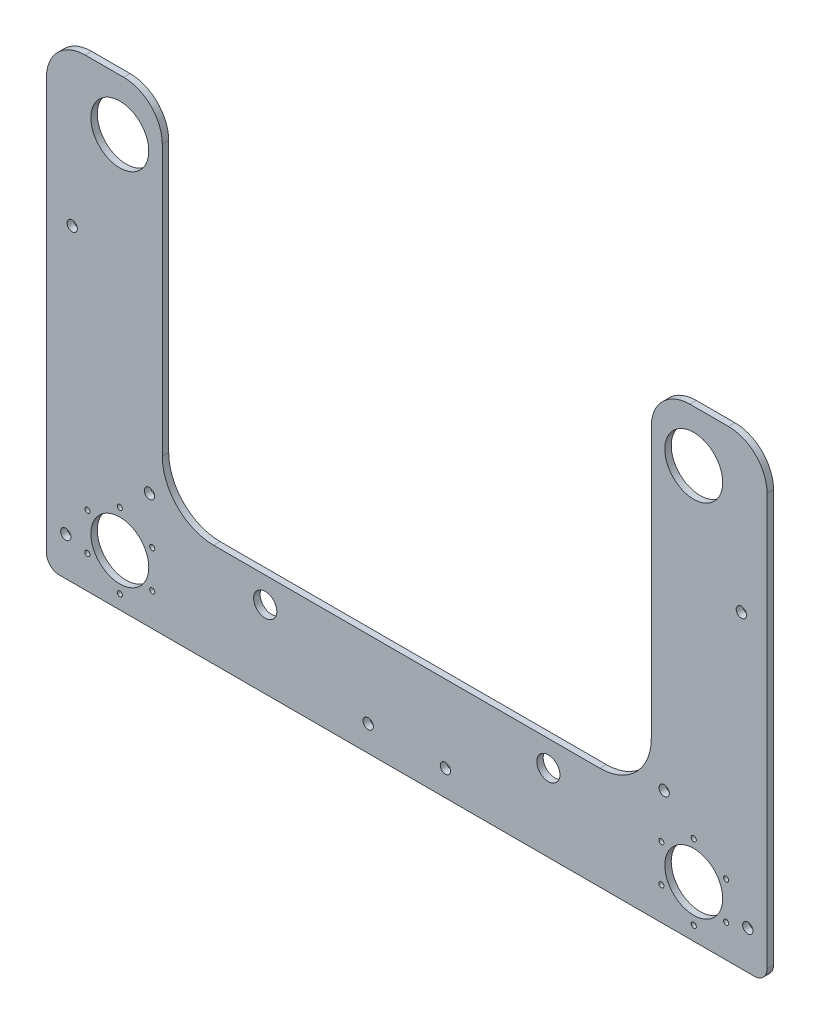
SolidWorks part; units mm, degrees
ref_plane "Front Plane" through (0, 0, 0) normal (0, 0, 1) x (1, 0, 0)
ref_plane "Top Plane" through (0, 0, 0) normal (0, 1, 0) x (1, 0, 0)
ref_plane "Right Plane" through (0, 0, 0) normal (1, 0, 0) x (0, 0, -1)
sketch "Sketch1" plane through (0, 0, 0) normal (0, 0, 1) x (1, 0, 0)
  line L5 (120.65, -152.4) -> (120.65, -6.35)
  line L6 (127, 0) -> (171.45, 0) construction
  line L7 (177.8, -6.35) -> (177.8, -222.25)
  line L10 (0, -206.2199) -> (0, -63.6275) construction
  line L11 (-54.9244, 0) -> (300.6756, 0) construction
  line L13 (12.7, -177.8) -> (95.25, -177.8)
  line L14 (12.7, -228.6) -> (171.45, -228.6)
  line L15 (141.605, -25.4) -> (141.605, -84.2822) construction
  line L16 (141.605, -25.4) -> (141.605, -127) construction
  line L17 (-141.605, -25.4) -> (-141.605, -203.2) construction
  line L18 (-141.605, -25.4) -> (-141.605, -127) construction
  line L19 (-141.605, -19.05) -> (-141.605, -77.9322) construction
  line L20 (141.605, -25.4) -> (141.605, -203.2) construction
  line L22 (-120.65, -152.4) -> (-120.65, -6.35)
  line L23 (-12.7, -177.8) -> (-95.25, -177.8)
  line L24 (-12.7, -228.6) -> (-171.45, -228.6)
  line L25 (-177.8, -6.35) -> (-177.8, -222.25)
  line L26 (-12.7, -177.8) -> (12.7, -177.8)
  line L27 (-12.7, -228.6) -> (12.7, -228.6)
  line L28 (-177.8, -6.35) -> (-177.8, 6.35)
  line L29 (-165.1, 19.05) -> (-133.35, 19.05)
  line L30 (-120.65, 6.35) -> (-120.65, -6.35)
  line L31 (120.65, 6.35) -> (120.65, -6.35)
  line L32 (177.8, -6.35) -> (177.8, 6.35)
  line L33 (165.1, 19.05) -> (133.35, 19.05)
  arc A0 (95.25, -177.8) -> (120.65, -152.4) centre (95.25, -152.4) ccw
  arc A4 (120.65, -6.35) -> (127, 0) centre (127, -6.35) cw construction
  circle A8 centre (141.605, -25.4) radius 14.2875
  circle A9 centre (141.605, -25.4) radius 38.1 construction
  arc A10 (177.8, -6.35) -> (171.45, 0) centre (171.45, -6.35) ccw construction
  arc A11 (171.45, -228.6) -> (177.8, -222.25) centre (171.45, -222.25) ccw
  arc A14 (141.605, -82.55) -> (120.9214, -78.6758) centre (141.605, -25.4) ccw construction
  arc A15 (-141.605, -82.55) -> (-120.9214, -78.6758) centre (-141.605, -25.4) cw construction
  circle A16 centre (-141.605, -25.4) radius 38.1 construction
  circle A17 centre (-141.605, -25.4) radius 14.2875
  arc A19 (-95.25, -177.8) -> (-120.65, -152.4) centre (-95.25, -152.4) cw
  circle A20 centre (141.605, -127) radius 38.1 construction
  circle A21 centre (-141.605, -127) radius 38.1 construction
  arc A23 (-171.45, -228.6) -> (-177.8, -222.25) centre (-171.45, -222.25) cw
  circle A24 centre (-141.605, -203.2) radius 14.2875
  circle A25 centre (-141.605, -184.7225) radius 1.27
  circle A26 centre (-125.603, -193.9612) radius 1.27
  circle A27 centre (-125.603, -212.4388) radius 1.27
  circle A28 centre (-141.605, -221.6775) radius 1.27
  circle A29 centre (-157.607, -212.4388) radius 1.27
  circle A30 centre (-157.607, -193.9612) radius 1.27
  circle A31 centre (157.607, -212.4388) radius 1.27
  circle A32 centre (157.607, -193.9612) radius 1.27
  circle A33 centre (141.605, -184.7225) radius 1.27
  circle A34 centre (125.603, -193.9612) radius 1.27
  circle A35 centre (125.603, -212.4388) radius 1.27
  circle A36 centre (141.605, -221.6775) radius 1.27
  circle A37 centre (141.605, -203.2) radius 14.2875
  circle A39 centre (-69.85, -190.5) radius 5.715
  circle A40 centre (69.85, -190.5) radius 5.715
  circle A42 centre (-19.05, -215.9) radius 2.54
  circle A43 centre (-127, -171.45) radius 2.54
  arc A44 (-133.35, 19.05) -> (-120.65, 6.35) centre (-133.35, 6.35) cw
  arc A45 (-177.8, 6.35) -> (-165.1, 19.05) centre (-165.1, 6.35) cw
  arc A46 (133.35, 19.05) -> (120.65, 6.35) centre (133.35, 6.35) ccw
  arc A47 (177.8, 6.35) -> (165.1, 19.05) centre (165.1, 6.35) ccw
  circle A50 centre (-149.225, 6.35) radius 2.54
  circle A51 centre (127, -171.45) radius 2.54
  circle A53 centre (149.225, 6.35) radius 2.54
  circle A54 centre (-168.275, -209.55) radius 2.54
  circle A56 centre (168.275, -209.55) radius 2.54
  circle A58 centre (-165.1, -76.2) radius 2.54
  circle A59 centre (165.1, -76.2) radius 2.54
  circle A60 centre (19.05, -215.9) radius 2.54
  point P2 (177.8, -44.45)
  point P18 (177.8, 0)
  point P23 (177.8, -228.6)
  point P24 (177.8, -228.6)
  point P31 (177.8, 0)
  point P48 (-177.8, 0)
  point P49 (-177.8, -228.6)
  point P51 (-177.8, -44.45)
  point P78 (-141.605, -203.2)
  point P118 (0, 0)
  point P119 (0, 0)
  point P120 (-20.2977, -209.55)
  dimension "D6" = 25.4
  dimension "D7" = 6.35
  dimension "D8" = 6.35
  dimension "D9" = 177.8
  dimension "D10" = 28.575
  dimension "D12" = 76.2
  dimension "D13" = 57.15
  dimension "D15" = 28.575
  dimension "D18" = 76.2
  dimension "D21" = 2.54
  dimension "D29" = 9.525
  dimension "D32" = 11.43
  dimension "D35" = 5.08
  dimension "D37" = 5.08
  dimension "D40" = 12.7
  dimension "D43" = 5.08
  dimension "D45" = 12.7
  dimension "D30" = 5.08
  dimension "D41" = 5.08
  dimension "D2" = 120.65
  dimension "D3" = 177.8
  dimension "D4" = 228.6
  dimension "D5" = 177.8
  dimension "D11" = 20.955
  dimension "`" = 25.4
  dimension "D14" = 57.15
  dimension "D16" = 184.15
  dimension "D17" = 101.6
  dimension "D19" = 25.4
  dimension "D20" = 107.95
  dimension "D22" = 0
  dimension "D23" = 18.4775
  dimension "D25" = 6.9225
  dimension "D26" = 19.05
  dimension "D27" = 25.4
  dimension "D28" = 25.4
  dimension "D31" = 95.25
  dimension "D33" = 12.7
  dimension "D34" = 38.1
  dimension "D36" = 12.7
  dimension "D38" = 57.15
  dimension "D39" = 19.05
  dimension "D42" = 6.35
  dimension "D44" = 28.575
  dimension "D46" = 19.05
  dimension "D24" = 6
extrude "Boss-Extrude3" add sketch "Sketch1" along normal blind 3.175
sketch "Sketch2" plane through (0, 0, 3.175) normal (0, 0, 1) x (1, 0, 0)
  line L0 (-133.35, 19.05) -> (-165.1, 19.05) construction
  line L1 (-177.8, 19.05) -> (177.8, 19.05)
  line L2 (-177.8, 19.05) -> (-177.8, 0)
  line L3 (-177.8, 0) -> (177.8, 0)
  line L4 (177.8, 19.05) -> (177.8, 0)
  line L5 (-177.8, 6.35) -> (-177.8, -222.25) construction
  line L6 (177.8, -222.25) -> (177.8, 6.35) construction
  dimension "D1" = 19.05
extrude "Cut-Extrude1" cut sketch "Sketch2" against normal through all
fillet "Fillet1" radius 19.05 4 edges at (177.8, 0, 1.5875) (120.65, 0, 1.5875) (-120.65, 0, 1.5875) (-177.8, 0, 1.5875)
